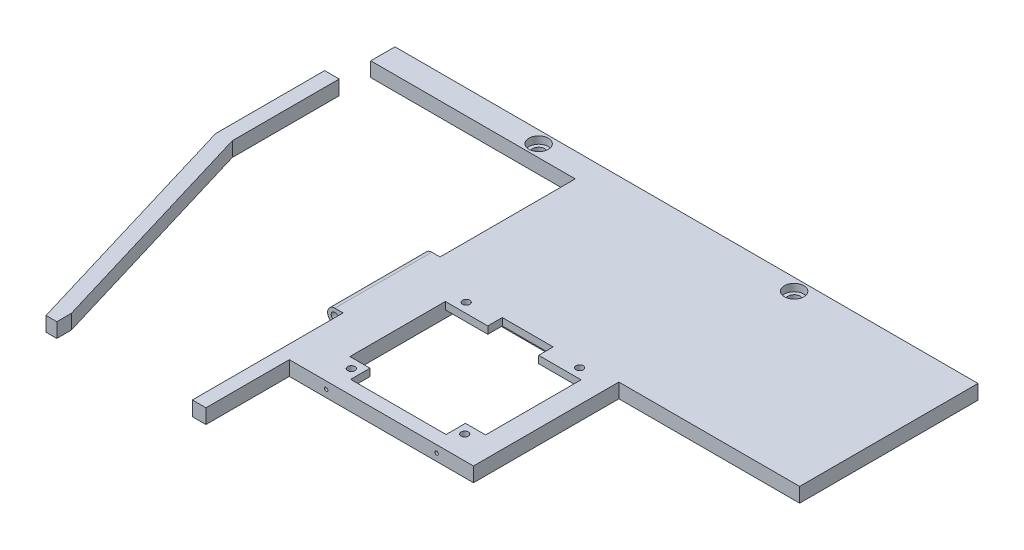
SolidWorks part; units mm, degrees
ref_plane "前视基准面" through (0, 0, 0) normal (0, 0, 1) x (1, 0, 0)
ref_plane "上视基准面" through (0, 0, 0) normal (0, 1, 0) x (1, 0, 0)
ref_plane "右视基准面" through (0, 0, 0) normal (1, 0, 0) x (0, 0, -1)
other "Configuration Table"
sketch "草图1" plane through (0, 0, 0) normal (0, 1, 0) x (1, 0, 0)
  line L1 (-60, -17) -> (60, -17)
  line L2 (-60, -17) -> (-60, 17)
  line L3 (-60, 17) -> (60, 17)
  line L4 (60, -17) -> (60, 17)
  line L5 (-60, -17) -> (60, 17) construction
  line L6 (-60, 17) -> (60, -17) construction
  point P0 (0, 0)
  dimension "D1" = 120
  dimension "D5" = 34
extrude "凸台-拉伸1" add sketch "草图1" along normal blind 3 contours L3 L4 L1 L2
sketch "草图2" plane through (0, 3, 0) normal (0, 1, 0) x (1, 0, 0)
  circle A2 centre (-24.8571, 14.5) radius 1.25
  circle A3 centre (-24.8571, 14.5) radius 2
  circle A8 centre (27.8571, 14.5) radius 1.25
  circle A9 centre (27.8571, 14.5) radius 2
  dimension "D1" = 2.5
  dimension "D2" = 4
extrude "切除-拉伸1" cut sketch "草图2" against normal through all contours A8 | A2
extrude "切除-拉伸2" cut sketch "草图2<3>" against normal blind 1.5 contours A3 | A9
sketch "草图2<3>" plane through (0, 3, 0) normal (0, 1, 0) x (1, 0, 0) same geometry as "草图2"
sketch "草图4" plane through (0, 0, 0) normal (0, 1, 0) x (1, 0, 0)
  line L0 (-12, -17) -> (-12, -67)
  line L1 (-12, -67) -> (-45, -67)
  line L2 (-45, -67) -> (-60, -17)
  line L3 (-60, -17) -> (-60, 17) construction
  line L4 (-60, -17) -> (60, -17) construction
  line L5 (-60, -17) -> (-60, 17) construction
  line L6 (-12, -17) -> (-60, -17)
  dimension "D1" = 50
  dimension "D2" = 33
  dimension "D3" = 48
extrude "凸台-拉伸2" add sketch "草图4" along normal up to surface (3 mm away) up to face at (-24.8571, 3, -12.5)
sketch "草图5" plane through (0, 3, 0) normal (0, 1, 0) x (1, 0, 0)
  line L0 (-15, 12) -> (-15, -64)
  line L1 (-57, 12) -> (-15, 12)
  line L2 (-57, 12) -> (-57, -16.5597)
  line L5 (-15, -64) -> (-42.7679, -64)
  line L6 (-42.7679, -64) -> (-57, -16.5597)
  line L8 (-60, 17) -> (60, 17) construction
  line L9 (-60, -17) -> (-60, 17) construction
  line L10 (-12, -17) -> (-12, -67) construction
  line L11 (-12, -67) -> (-45, -67) construction
  line L13 (-45, -67) -> (-60, -17) construction
  line L14 (-42.7679, -64) -> (-42.7679, -67)
  line L15 (-42.7679, -67) -> (-15, -67)
  line L16 (-15, -67) -> (-15, -64)
  line M14 (-45, -67) -> (-12, -67)
  dimension "D1" = 5
  dimension "D2" = 3
  dimension "D3" = 3
  dimension "D4" = 3
  dimension "D5" = 3
extrude "切除-拉伸3" cut sketch "草图5" against normal through all contours L6 L5 L0 L1 L2 | L16 L5 L14 M14 region at (-34.0774, 3, 23.376) region at (-28.884, 3, 65.5)
sketch "草图6" plane through (0, 0, 67) normal (0, 0, 1) x (1, 0, 0)
  line L0 (-57, 0) -> (-15, 0) construction
  line L1 (-15, 3) -> (-18, 3)
  line L2 (-15, 3) -> (-15, 0)
  line L3 (-15, 0) -> (-18, 0)
  line L4 (-18, 3) -> (-18, 0)
  circle A0 centre (-16.5, 1.5) radius 1.5
  circle A1 centre (-16.5, 1.5) radius 0.75
  line M7 (-15, 3) -> (-15, 0)
  dimension "D1" = 1.5
extrude "凸台-拉伸3" add sketch "草图6" against normal up to surface (79 mm away) contours A0 A1 | A0 L1 M7 | A0 L3 L2 region at (-15.3351, 2.6649, 67) region at (-15.4693, 2.5307, 67) region at (-15.3351, 0.3351, 67) up to face at (-36, 1.5, -12)
sketch "草图7" plane through (0, 3, 0) normal (0, 1, 0) x (1, 0, 0)
  line L5 (-57, 12) -> (-16.5, 12) construction
  line L7 (-18, 12) -> (-14.8, 12)
  line L12 (-18, 12) -> (-18, -15.8999)
  line L14 (-18, -15.8999) -> (-14.8, -15.8999)
  line L15 (-14.8, 12) -> (-14.8, -15.8999)
  line L16 (-18, 12) -> (-18, -67) construction
  line L17 (-14.8, -15.8999) -> (-18, -15.8999)
  line L18 (-14.8, -15.8999) -> (-14.8, -35.8999)
  line L19 (-14.8, -35.8999) -> (-18, -35.8999)
  line L20 (-18, -15.8999) -> (-18, -35.8999)
  line L21 (-12, -67) -> (-16.5, -67) construction
  line L22 (-18, -35.8999) -> (-14.8, -35.8999)
  line L23 (-18, -35.8999) -> (-18, -67)
  line L24 (-18, -67) -> (-14.8, -67)
  line L25 (-14.8, -35.8999) -> (-14.8, -67)
  line L26 (-18, -63.8) -> (-14.8, -63.8)
  line L27 (-16.4, -15.8999) -> (-16.5, 12) construction
  line L28 (-16.5, 12) -> (-16.5, -67) construction
  line L29 (-16.4, -35.8999) -> (-16.4, -63.8) construction
  line M14 (-57, 12) -> (-16.5, 12)
  line M15 (-16.5, 12) -> (-16.5, -67)
  line M16 (-16.5, -67) -> (-12, -67)
  dimension "D1" = 3.2
  dimension "D2" = 20
  dimension "D3" = 3.2
extrude "切除-拉伸5" cut sketch "草图7" against normal through all contours L26 L23 L24 M15 | L26 L25 M15 M16 | L26 L25 L19 M15 | L23 L26 L19 M15 | L15 L7 L14 M15 | L12 L14 M15 M14 region at (-17.25, 3, 1.95) region at (-15.65, 3, 1.95) region at (-17.25, 3, 49.85) region at (-15.65, 3, 49.85) region at (-17.25, 3, 65.4) region at (-15.65, 3, 65.4)
sketch "草图9" plane through (0, 0, 0) normal (0, -1, 0) x (1, 0, 0)
  line L0 (-60, -17) -> (60, -17) construction
  line L1 (-60, -17) -> (-57, -17)
  line L2 (-60, -17) -> (-60, -5.5)
  line L3 (-60, -5.5) -> (-57, -5.5)
  line L4 (-57, -17) -> (-57, -5.5)
  line L5 (-60, 17) -> (-60, -17) construction
  line L6 (-57, -12) -> (-57, 16.5597) construction
  dimension "D1" = 11.5
extrude "切除-拉伸8" cut sketch "草图9" against normal through all
sketch "草图10" plane through (0, 0, 0) normal (0, -1, 0) x (1, 0, 0)
  line L0 (-58, -5.5) -> (-58, 16.7065)
  line L1 (-57, -5.5) -> (-60, -5.5) construction
  line L2 (-58, 16.7065) -> (-43.2119, 66)
  line L3 (-43.2119, 66) -> (-44.256, 66)
  line L4 (-44.256, 66) -> (-59, 16.8532)
  line L5 (-59, 16.8532) -> (-59, -5.5)
  line L6 (-59, -5.5) -> (-58, -5.5)
  line L7 (-57, -5.5) -> (-57, 16.5597) construction
  line L8 (-42.7679, 64) -> (-57, 16.5597) construction
  line L10 (-45, 67) -> (-42.7679, 67) construction
  dimension "D1" = 1
  dimension "D2" = 1
  dimension "D3" = 1
  dimension "D4" = 1
  dimension "D5" = 1
extrude "切除-拉伸9" cut sketch "草图10" against normal blind 1.5
sketch "草图12" plane through (-57, 0, 0) normal (-1, 0, 0) x (0, 0, 1)
  line L0 (-12, 0) -> (-17, 3) construction
  line L1 (-17, 0) -> (-12, 0) construction
  line L2 (-12, 0) -> (-12, 3) construction
  line L3 (-17, 3) -> (-17, 0) construction
  circle A0 centre (-14.5, 1.5) radius 0.35
  dimension "D1" = 0.7
extrude "切除-拉伸10" cut sketch "草图12" against normal blind 3
sketch "草图17" plane through (0, 3, 0) normal (0, 1, 0) x (1, 0, 0)
  line L0 (60, -17) -> (60, 17) construction
  line L1 (60, 17) -> (63.3, 17)
  line L2 (60, 17) -> (60, -19.8)
  line L3 (60, -19.8) -> (63.3, -19.8)
  line L4 (63.3, 17) -> (63.3, -19.8)
  line L5 (-12, -17) -> (60, -17) construction
  line L6 (60, -19.8) -> (-12, -19.8)
  line L7 (60, -19.8) -> (60, -17)
  line L8 (60, -17) -> (-12, -17)
  line L9 (-12, -19.8) -> (-12, -17)
  line L10 (-57, 17) -> (60, 17) construction
  line L11 (-12, -17) -> (-12, -67) construction
  line L13 (-12, -19.8) -> (26, -19.8)
  line L14 (-12, -19.8) -> (-12, -49.8)
  line L15 (-12, -49.8) -> (26, -49.8)
  line L16 (26, -19.8) -> (26, -49.8)
  line M26 (-12, -67) -> (-12, -17)
  line M27 (-12, -17) -> (60, -17)
  line M28 (60, -17) -> (60, 17)
  dimension "D1" = 3.3
  dimension "D2" = 2.8
  dimension "D3" = 38
  dimension "D4" = 30
extrude "凸台-拉伸4" add sketch "草图17" against normal up to surface (3 mm away) contours L4 L1 L2 L3 M28 | L6 L2 M27 M26 | L16 L6 L15 M26 | L14 L13 L16 L15 region at (61.65, 3, 1.4) region at (24, 3, 18.4) region at (7, 3, 34.8) up to face at (-52.7695, 0, 28.8553)
sketch "草图13" plane through (0, 3, 0) normal (0, 1, 0) x (1, 0, 0)
  line L1 (-12, -49.8) -> (-12, -67) construction
  circle A0 centre (19.4, -45) radius 0.75
  circle A1 centre (-4, -45) radius 0.75
  circle A2 centre (19.4, -21.3) radius 0.75
  circle A3 centre (-4, -21.3) radius 0.75
  dimension "D1" = 1.5
  dimension "D2" = 23.4
  dimension "D3" = 23.7
  dimension "D4" = 45
  dimension "D5" = 8
extrude "切除-拉伸11" cut sketch "草图13" against normal through all
sketch "草图15" plane through (0, 3, 0) normal (0, 1, 0) x (1, 0, 0)
  line L1 (17.55, -47) -> (-2.15, -47)
  line L2 (17.55, -47) -> (17.55, -43)
  line L3 (17.55, -43) -> (-2.15, -43)
  line L4 (-2.15, -47) -> (-2.15, -43)
  line L5 (-6.3, -43) -> (21.7, -43)
  line L6 (-6.3, -43) -> (-6.3, -23.3)
  line L7 (-6.3, -23.3) -> (21.7, -23.3)
  line L8 (21.7, -43) -> (21.7, -23.3)
  line L9 (12.95, -23.3) -> (2.45, -23.3)
  line L10 (12.95, -23.3) -> (12.95, -20.3)
  line L11 (12.95, -20.3) -> (2.45, -20.3)
  line L12 (2.45, -23.3) -> (2.45, -20.3)
  line L14 (21.7, -23.3) -> (12.95, -20.3) construction
  line L15 (2.45, -20.3) -> (-6.3, -23.3) construction
  circle A0 centre (-4, -45) radius 0.75 construction
  circle A1 centre (-4, -21.3) radius 0.75 construction
  dimension "D1" = 2
  dimension "D6" = 1.85
  dimension "D2" = 28
  dimension "D3" = 4.15
  dimension "D4" = 4
  dimension "D5" = 4.15
  dimension "D7" = 2
  dimension "D8" = 3
  dimension "D9" = 10.5
extrude "切除-拉伸14" cut sketch "草图15" against normal through all contours L5 L8 L7 L6 L3 | L4 L1 L2 L3 | L12 L7 L10 L11 region at (7.7, 3, 45) region at (7.7, 3, 33.15) region at (7.7, 3, 21.8)
sketch "草图16" plane through (0, 0, 0) normal (0, 1, 0) x (1, 0, 0)
  line L1 (-6.3, -47.3) -> (21.7, -47.3)
  line L2 (-6.3, -47.3) -> (-6.3, -19)
  line L3 (-6.3, -19) -> (21.7, -19)
  line L4 (21.7, -47.3) -> (21.7, -19)
  circle A0 centre (19.4, -21.3) radius 0.75 construction
  circle A1 centre (-4, -21.3) radius 0.75 construction
  circle A2 centre (19.4, -45) radius 0.75 construction
  dimension "D3" = 2.3
  dimension "D1" = 2.3
  dimension "D2" = 2.3
  dimension "D4" = 2.3
extrude "切除-拉伸15" cut sketch "草图16" along normal blind 1.5
sketch "草图18" plane through (0, 0, 49.8) normal (0, 0, 1) x (1, 0, 0)
  circle A0 centre (18.4, 1.5) radius 0.35
  circle A1 centre (-4.4, 1.5) radius 0.35
  point P4 (0, 0)
  dimension "D1" = 0.7
extrude "切除-拉伸16" cut sketch "草图18" against normal blind 3
